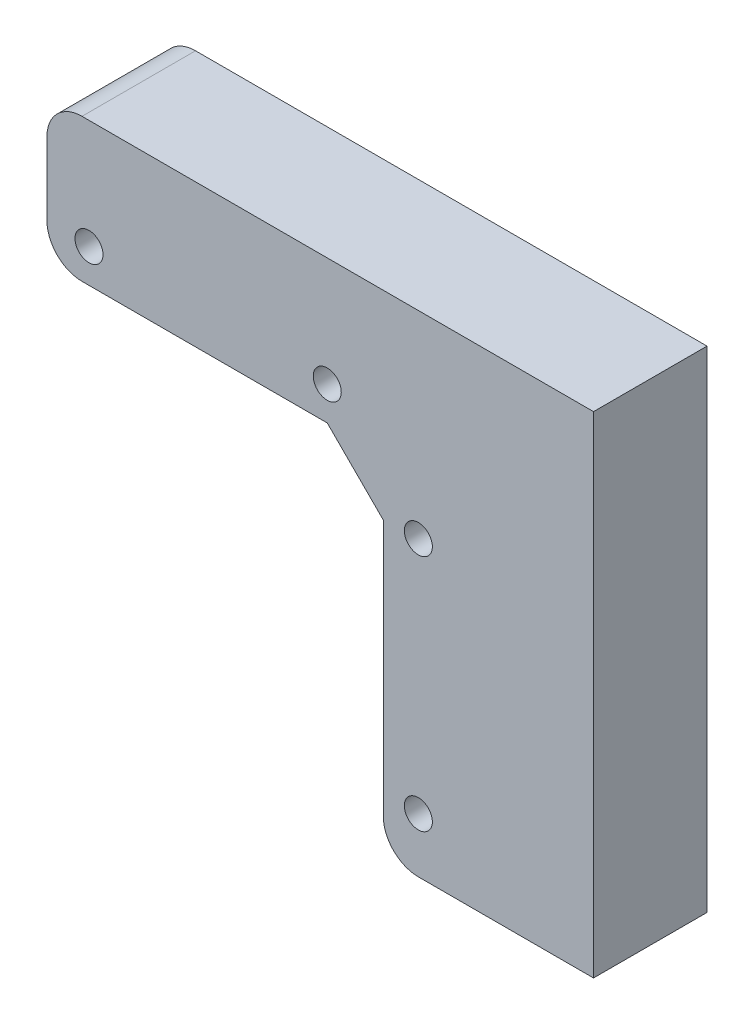
SolidWorks part; units mm, degrees
ref_plane "Plan de face" through (0, 0, 0) normal (0, 0, 1) x (1, 0, 0)
ref_plane "Plan de dessus" through (0, 0, 0) normal (0, 1, 0) x (1, 0, 0)
ref_plane "Plan de droite" through (0, 0, 0) normal (1, 0, 0) x (0, 0, -1)
sketch "Esquisse1" plane through (0, 0, 0) normal (0, 0, 1) x (1, 0, 0)
  line L1 (0, 0) -> (15, 0)
  line L2 (0, 0) -> (0, 35)
  line L3 (0, 35) -> (15, 35)
  line L4 (15, 0) -> (15, 35)
  dimension "D1" = 15
  dimension "D2" = 35
extrude "Boss.-Extru.1" add sketch "Esquisse1" along normal blind 8.1
sketch "Esquisse2" plane through (0, 0, 8.1) normal (0, 0, 1) x (1, 0, 0)
  line L1 (0, 35) -> (-24, 35)
  line L2 (0, 35) -> (0, 24.8)
  line L3 (0, 24.8) -> (-24, 24.8)
  line L4 (-24, 35) -> (-24, 24.8)
  dimension "D1" = 10.2
  dimension "D2" = 24
extrude "Boss.-Extru.2" add sketch "Esquisse2" against normal up to vertex (8.1 mm away) up to point (0, 35, 0)
sketch "Esquisse3" plane through (0, 0, 8.1) normal (0, 0, 1) x (1, 0, 0)
  line L0 (-21, 27.2) -> (-4, 27.2) construction
  line L1 (15, 35) -> (-24, 35) construction
  line L2 (0, 24.8) -> (0, 0) construction
  line L3 (2.5, 3.9) -> (2.5, 20.9) construction
  circle A0 centre (-4, 27.2) radius 1
  circle A1 centre (-21, 27.2) radius 1
  circle A2 centre (2.5, 20.9) radius 1
  circle A4 centre (2.5, 3.9) radius 1
  dimension "D1" = 2
  dimension "D5" = 17
  dimension "D6" = 6.5
  dimension "D7" = 6.3
  dimension "D2" = 7.8
  dimension "D3" = 17
  dimension "D4" = 4
extrude "Enlèv. mat.-Extru.1" cut sketch "Esquisse3" against normal through all
chamfer "Chanfrein1" distance 4 angle 45 1 edges at (0, 24.8, 4.05)
fillet "Congé1" radius 2.5 3 edges at (0, 0, 4.05) (-24, 35, 4.05) (-24, 24.8, 4.05)
